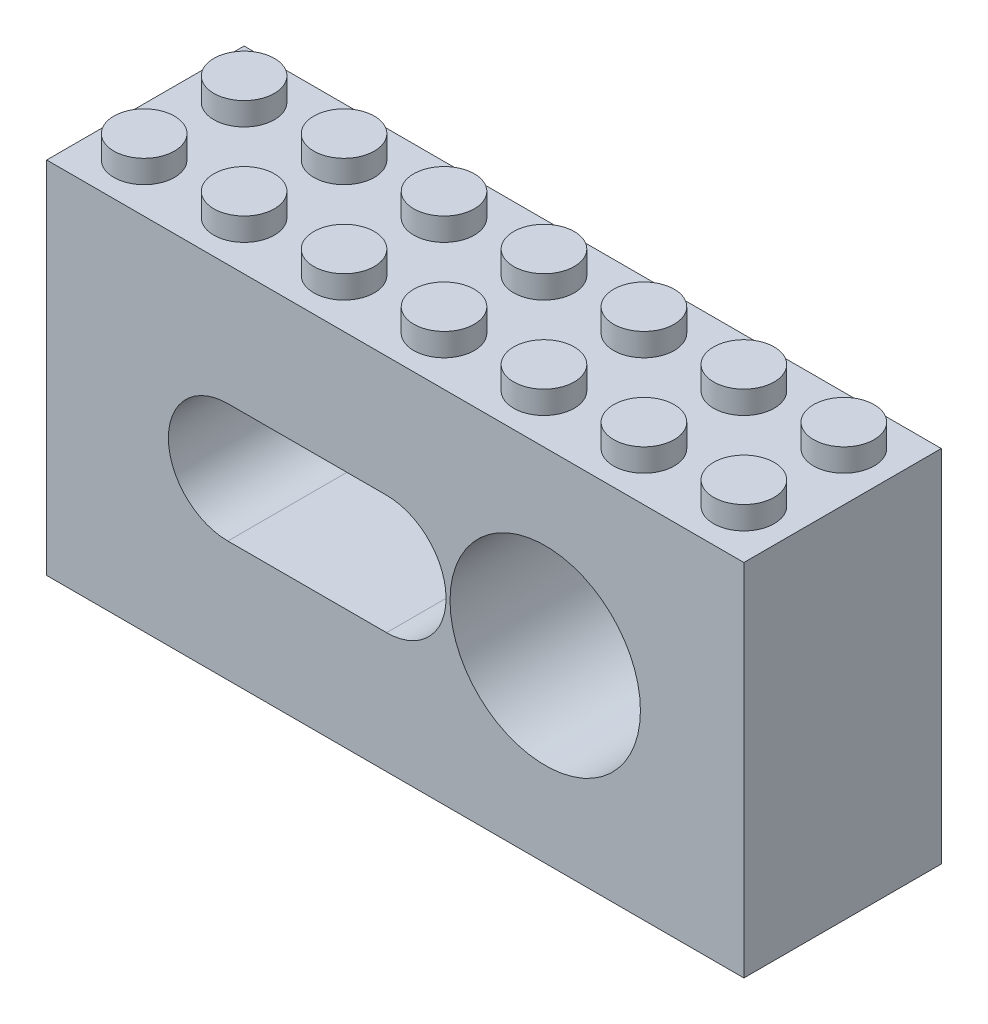
SolidWorks part; units mm, degrees
ref_plane "Front Plane" through (0, 0, 0) normal (0, 0, 1) x (1, 0, 0)
ref_plane "Top Plane" through (0, 0, 0) normal (0, 1, 0) x (1, 0, 0)
ref_plane "Right Plane" through (0, 0, 0) normal (1, 0, 0) x (0, 0, -1)
sketch "Sketch1" plane through (0, 0, 0) normal (0, 1, 0) x (1, 0, 0)
  line L1 (-39.0999, 16.0935) -> (16.7001, 16.0935)
  line L2 (-39.0999, 16.0935) -> (-39.0999, 0.2935)
  line L3 (-39.0999, 0.2935) -> (16.7001, 0.2935)
  line L4 (16.7001, 16.0935) -> (16.7001, 0.2935)
  dimension "D1" = 55.8
  dimension "D2" = 15.8
extrude "Boss-Extrude1" add sketch "Sketch1" along normal blind 28.8
sketch "Sketch2" plane through (0, 0, -0.2935) normal (0, 0, 1) x (1, 0, 0)
  line L0 (-39.0999, 0) -> (16.7001, 0) construction
  line L1 (-11.8999, 14.4) -> (-24.5999, 14.4) construction
  line L2 (-11.8999, 9.6375) -> (-24.5999, 9.6375)
  line L3 (-11.8999, 19.1625) -> (-24.5999, 19.1625)
  line L4 (16.7001, 28.8) -> (16.7001, 0) construction
  circle A0 centre (0.8001, 14.4) radius 7.62
  arc A1 (-11.8999, 9.6375) -> (-11.8999, 19.1625) centre (-11.8999, 14.4) ccw
  arc A2 (-24.5999, 19.1625) -> (-24.5999, 9.6375) centre (-24.5999, 14.4) ccw
  point P6 (-18.2499, 14.4)
  dimension "D4" = 15.24
  dimension "D5" = 4.7625
  dimension "D1" = 14.4
  dimension "D2" = 12.7
  dimension "D3" = 12.7
  dimension "D6" = 15.9
extrude "Cut-Extrude1" cut sketch "Sketch2" against normal blind 12.7
sketch "Sketch4" plane through (0, 0, -16.0935) normal (0, 0, -1) x (-1, 0, 0)
  line L0 (-16.7001, 28.8) -> (-16.7001, 0) construction
  circle A6 centre (-0.8001, 14.4) radius 2.7781
  circle A7 centre (11.8999, 14.4) radius 1.8415
  circle A8 centre (24.5999, 14.4) radius 1.8415
  dimension "D1" = 5.5563
  dimension "D2" = 3.683
  dimension "D3" = 3.683
  dimension "D4" = 12.7
  dimension "D5" = 12.7
  dimension "D6" = 15.9
extrude "Cut-Extrude2" cut sketch "Sketch4" against normal blind 12.7
sketch "Sketch5" plane through (0, 0, -16.0935) normal (0, 0, -1) x (-1, 0, 0)
  line L2 (24.5999, 19.1625) -> (11.8999, 19.1625)
  line L3 (11.8999, 9.6375) -> (24.5999, 9.6375)
  line L12 (24.5999, 19.1625) -> (11.8999, 19.1625)
  line L13 (11.8999, 9.6375) -> (24.5999, 9.6375)
  arc A2 (11.8999, 19.1625) -> (11.8999, 9.6375) centre (11.8999, 14.4) ccw
  arc A3 (24.5999, 9.6375) -> (24.5999, 19.1625) centre (24.5999, 14.4) ccw
  arc A4 (11.8999, 19.1625) -> (11.8999, 9.6375) centre (11.8999, 14.4) ccw
  arc A5 (24.5999, 9.6375) -> (24.5999, 19.1625) centre (24.5999, 14.4) ccw
  dimension "D2" = 0
extrude "Cut-Extrude6" cut sketch "Sketch5" against normal blind 1.905
sketch "Sketch6" plane through (0, 28.8, 0) normal (0, 1, 0) x (1, 0, 0)
  line L1 (16.7001, 16.0935) -> (-39.0999, 16.0935) construction
  line L3 (16.7001, 0.2935) -> (16.7001, 16.0935) construction
  circle A0 centre (12.8001, 12.1935) radius 2.425
  circle A1 centre (12.8001, 4.1935) radius 2.425
  circle A2 centre (4.8001, 12.1935) radius 2.425
  circle A3 centre (4.8001, 4.1935) radius 2.425
  circle A4 centre (-3.1999, 12.1935) radius 2.425
  circle A5 centre (-3.1999, 4.1935) radius 2.425
  circle A6 centre (-11.1999, 12.1935) radius 2.425
  circle A7 centre (-11.1999, 4.1935) radius 2.425
  circle A8 centre (-19.1999, 12.1935) radius 2.425
  circle A9 centre (-19.1999, 4.1935) radius 2.425
  circle A10 centre (-27.1999, 12.1935) radius 2.425
  circle A11 centre (-27.1999, 4.1935) radius 2.425
  circle A12 centre (-35.1999, 12.1935) radius 2.425
  circle A13 centre (-35.1999, 4.1935) radius 2.425
  dimension "D1" = 4.85
  dimension "D2" = 4.85
  dimension "D3" = 8
  dimension "D5" = 3.9
  dimension "D6" = 3.9
  dimension "D4" = 7
extrude "Boss-Extrude2" add sketch "Sketch6" along normal blind 1.83
sketch "Sketch7" plane through (0, 0, 0) normal (0, -1, 0) x (1, 0, 0)
  line L0 (-39.0999, -16.0935) -> (-39.0999, -0.2935) construction
  line L1 (-37.8799, -1.5135) -> (15.4801, -1.5135)
  line L2 (-37.8799, -1.5135) -> (-37.8799, -14.8735)
  line L3 (-37.8799, -14.8735) -> (15.4801, -14.8735)
  line L4 (15.4801, -1.5135) -> (15.4801, -14.8735)
  line L5 (-39.0999, -0.2935) -> (16.7001, -0.2935) construction
  line L6 (16.7001, -0.2935) -> (16.7001, -16.0935) construction
  line L7 (16.7001, -16.0935) -> (-39.0999, -16.0935) construction
  line L8 (-39.0999, -0.2935) -> (-39.0999, -16.0935)
  circle A0 centre (-31.1999, -8.1935) radius 3.2625
  circle A1 centre (-23.1999, -8.1935) radius 3.2625
  circle A2 centre (-15.1999, -8.1935) radius 3.2625
  circle A3 centre (-7.1999, -8.1935) radius 3.2625
  circle A4 centre (0.8001, -8.1935) radius 3.2625
  circle A5 centre (8.8001, -8.1935) radius 3.2625
  dimension "D5" = 6.525
  dimension "D1" = 1.22
  dimension "D2" = 1.22
  dimension "D3" = 1.22
  dimension "D4" = 1.22
  dimension "D6" = 7.9
  dimension "D7" = 7.9
  dimension "D8" = 15.8
  dimension "D9" = 6
extrude "Cut-Extrude7" cut sketch "Sketch7" against normal blind 3 contours L4 L1 L2 L3 A5 A4 A3 A2 A1 A0 region at (-11.1999, 0, -8.1935)
